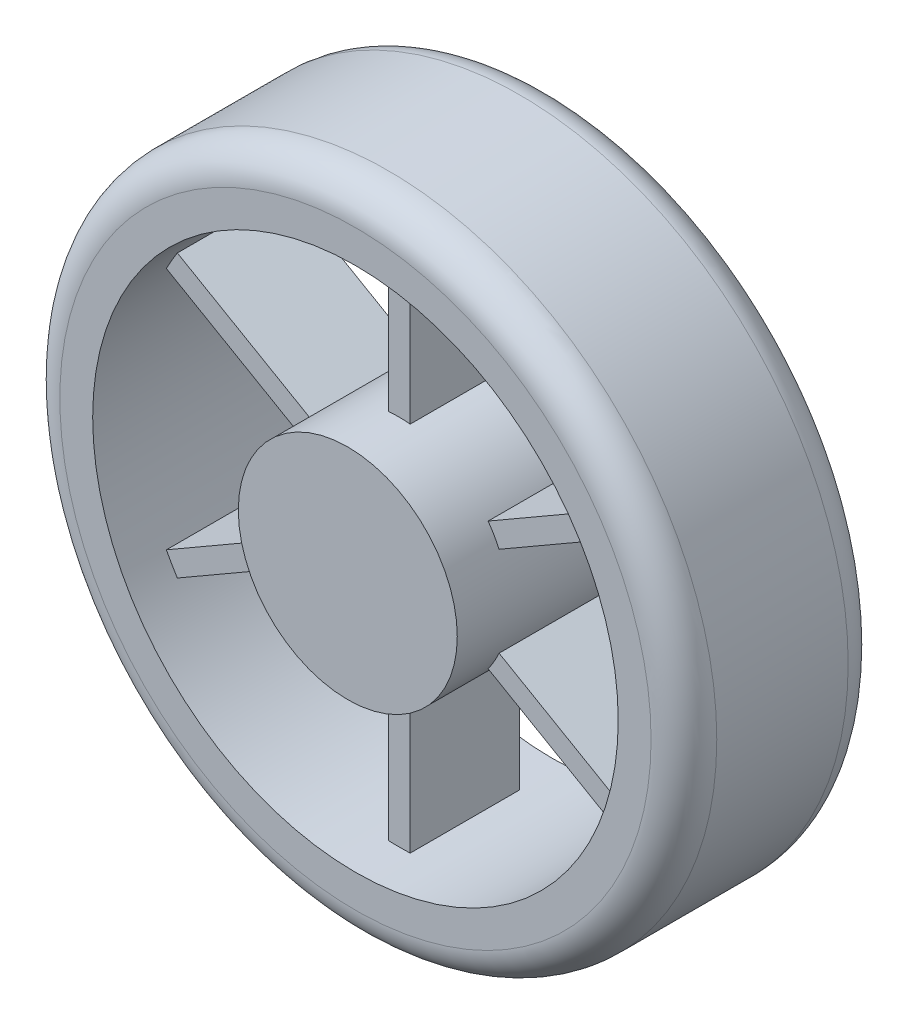
SolidWorks part; units mm, degrees
ref_plane "Front Plane" through (0, 0, 0) normal (0, 0, 1) x (1, 0, 0)
ref_plane "Top Plane" through (0, 0, 0) normal (0, 1, 0) x (1, 0, 0)
ref_plane "Right Plane" through (0, 0, 0) normal (1, 0, 0) x (0, 0, -1)
sketch "Sketch1" plane through (0, 0, 0) normal (0, 0, 1) x (1, 0, 0)
  circle A0 centre (0, 0) radius 50
  dimension "D1" = 100
extrude "Boss-Extrude1" add sketch "Sketch1" along normal mid plane 97
sketch "Sketch2" plane through (0, 0, 0) normal (0, 0, 1) x (1, 0, 0)
  circle A0 centre (0, 0) radius 150
  circle A1 centre (0, 0) radius 120
  dimension "D1" = 300
  dimension "D2" = 30
extrude "Boss-Extrude2" add sketch "Sketch2" along normal mid plane 90 separate body
sketch "Sketch3" plane through (0, 0, 0) normal (0, 0, 1) x (1, 0, 0)
  line L0 (0, 50) -> (0, 120) construction
  line L3 (-5, 119.8958) -> (-5, 49.7494)
  line L4 (5, 119.8958) -> (5, 49.7494)
  arc A4 (5, 49.7494) -> (-5, 49.7494) centre (0, 0) ccw
  arc A5 (5, 119.8958) -> (-5, 119.8958) centre (0, 0) ccw
  dimension "D1" = 100
  dimension "D2" = 240
  dimension "D3" = 5
extrude "Boss-Extrude3" add sketch "Sketch3" along normal mid plane 50
ref_axis "Axis2" through (0, 0, -53.35) along (0, 0, 1)
pattern_circular "CirPattern15" count 6 over 360 about axis through (0, 0, -53.35) along (0, 0, 1) of "Boss-Extrude3"
fillet "Fillet1" radius 15 2 edges at (150, 0, -45) (150, 0, 45)
